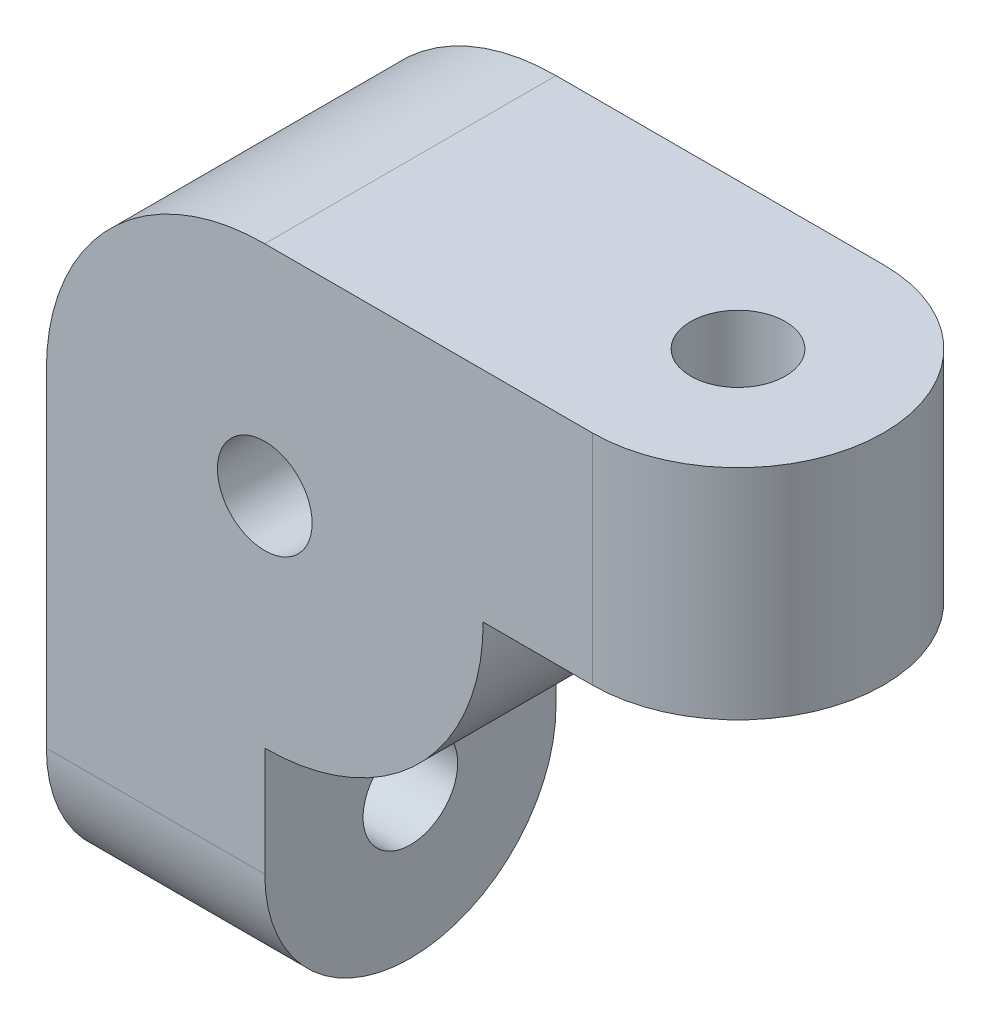
SolidWorks part; units mm, degrees
ref_plane "Front Plane" through (0, 0, 0) normal (0, 0, 1) x (1, 0, 0)
ref_plane "Top Plane" through (0, 0, 0) normal (0, 1, 0) x (1, 0, 0)
ref_plane "Right Plane" through (0, 0, 0) normal (1, 0, 0) x (0, 0, -1)
sketch "Sketch1" plane through (0, 0, 0) normal (0, 0, 1) x (1, 0, 0)
  line L0 (-6, 0) -> (-6, -6)
  line L1 (-6, -6) -> (0, -6)
  line L2 (0, 6) -> (6, 6)
  line L3 (6, 6) -> (6, 0)
  circle A0 centre (0, 0) radius 6
  circle A1 centre (0, 0) radius 1.3
  dimension "D1" = 12
  dimension "D2" = 2.6
extrude "Boss-Extrude1" add sketch "Sketch1" along normal blind 8 contours A0 A1 | A0 L0 L1 | A0 L3 L2 region at (-4.6598, -4.6598, 0) region at (-4.1226, 4.1226, 0) region at (4.6598, 4.6598, 0)
sketch "Sketch4" plane through (0, 0, 0) normal (1, 0, 0) x (0, 0, -1)
  line L1 (-8, -9) -> (0, -9)
  line L2 (-8, -9) -> (-8, -6)
  line L3 (-8, -6) -> (0, -6)
  line L4 (0, -6) -> (0, -9)
  arc A0 (-8, -9) -> (0, -9) centre (-4, -9) ccw
  dimension "D1" = 3
extrude "Boss-Extrude2" add sketch "Sketch4" against normal blind 6 contours L4 L3 L2 L1 | L1 A0 region at (0, -7.5, 4) region at (0, -10.6977, 4)
sketch "Sketch5" plane through (0, 0, 0) normal (0, 1, 0) x (1, 0, 0)
  line L1 (6, 0) -> (9, 0)
  line L2 (6, 0) -> (6, -8)
  line L3 (6, -8) -> (9, -8)
  arc A1 (9, -8) -> (9, 0) centre (9, -4) ccw
  dimension "D1" = 3
extrude "Boss-Extrude4" add sketch "Sketch5" along normal blind 6
sketch "Sketch12" plane through (0, 0, 0) normal (0, -1, 0) x (1, 0, 0)
  circle A0 centre (9, 4) radius 1.3
  dimension "D1" = 2.6
extrude "Cut-Extrude6" cut sketch "Sketch12" against normal blind 6
sketch "Sketch13" plane through (0, 0, 0) normal (1, 0, 0) x (0, 0, -1)
  circle A0 centre (-4, -9) radius 1.3
  dimension "D1" = 2.6
extrude "Cut-Extrude7" cut sketch "Sketch13" against normal blind 6
sketch "Sketch14" plane through (0, 0, 0) normal (0, 0, -1) x (-1, 0, 0)
  circle A0 centre (0, 0) radius 3
  dimension "D1" = 6
extrude "Cut-Extrude8" cut sketch "Sketch14" against normal blind 3
